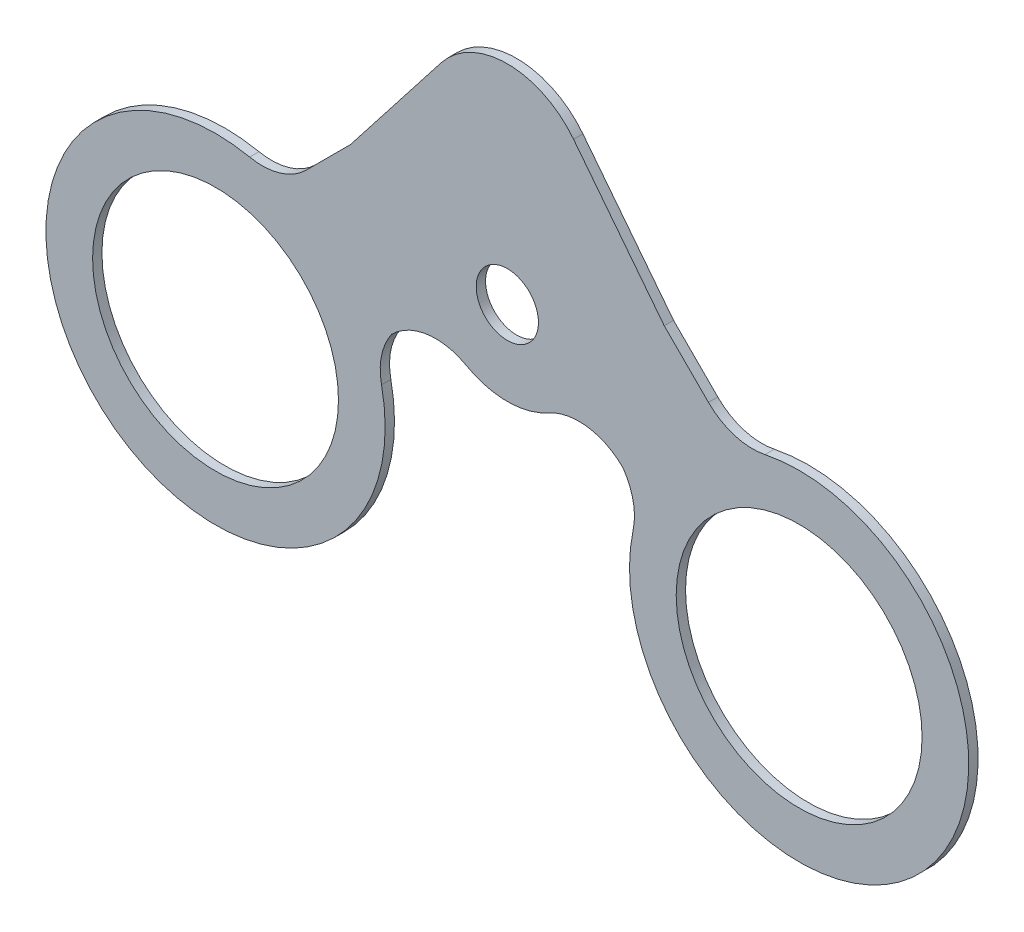
SolidWorks part; units mm, degrees
ref_plane "Спереди" through (0, 0, 0) normal (0, 0, 1) x (1, 0, 0)
ref_plane "Сверху" through (0, 0, 0) normal (0, 1, 0) x (1, 0, 0)
ref_plane "Справа" through (0, 0, 0) normal (1, 0, 0) x (0, 0, -1)
sketch "Эскиз1" plane through (0, 0, 0) normal (0, 0, 1) x (1, 0, 0)
  line L0 (-93.75, 0) -> (93.75, 0) construction
  line L1 (-93.75, 0) -> (0, 53.75) construction
  line L2 (0, 53.75) -> (93.75, 0) construction
  line L3 (93.75, 0) -> (93.75, -40) construction
  line L4 (0, 53.75) -> (53.75, -40) construction
  line L5 (93.75, -40) -> (53.75, -40) construction
  line L26 (0, 53.75) -> (-93.75, 53.75) construction
  line L27 (-93.75, 0) -> (0, 93.75) construction
  line L28 (0, 93.75) -> (93.75, 0) construction
  line L29 (-73.0386, 50.4112) -> (-50.4112, 73.0386)
  line L30 (-23.5342, 40.516) -> (-43.3388, 20.7114)
  line L31 (-61.7249, 61.7249) -> (-32.0251, 32.0251) construction
  line L32 (43.3388, 20.7114) -> (23.5342, 40.516)
  line L33 (73.0386, 50.4112) -> (50.4112, 73.0386)
  line L36 (-50.4112, 73.0386) -> (-21.2856, 110.3609)
  line L37 (50.4112, 73.0386) -> (21.2856, 110.3609)
  circle A0 centre (0, 53.75) radius 8.075 construction
  circle A3 centre (-93.75, 0) radius 39.5
  circle A4 centre (93.75, 0) radius 39.5
  arc A5 (-73.0386, 50.4112) -> (-43.3388, 20.7114) centre (-93.75, 0) ccw
  arc A6 (43.3388, 20.7114) -> (73.0386, 50.4112) centre (93.75, 0) ccw
  circle A8 centre (0, 53.75) radius 10
  circle A9 centre (0, 93.75) radius 20 construction
  circle A11 centre (0, 53.75) radius 20 construction
  circle A12 centre (-93.75, 0) radius 49.06 construction
  circle A13 centre (0, 93.75) radius 49.06 construction
  circle A17 centre (93.75, 0) radius 49.06 construction
  circle A18 centre (0, 93.75) radius 54.5 construction
  arc A20 (21.2856, 110.3609) -> (-21.2856, 110.3609) centre (0, 93.75) ccw
  circle A21 centre (0, 93.75) radius 27 construction
  circle A22 centre (-93.75, 0) radius 54.5 construction
  arc A23 (-23.5342, 40.516) -> (23.5342, 40.516) centre (0, 53.75) ccw
  circle A24 centre (93.75, 0) radius 54.5 construction
  point P2 (0, 0)
  point P28 (-46.875, 46.875)
  point P34 (0, 0)
  dimension "D6" = 16.15
  dimension "D4" = 79
  dimension "D8" = 20
  dimension "D9" = 40
  dimension "D11" = 98.12
  dimension "D1" = 187.5
  dimension "D2" = 53.75
  dimension "D3" = 40
  dimension "D10" = 29.827
  dimension "D13" = 32
  dimension "D12" = 7
  dimension "D5" = 15
  dimension "D7" = 15
  dimension "D14" = 7
extrude "Бобышка-Вытянуть1" add sketch "Эскиз1" along normal blind 3
fillet "Скругление1" radius 20 2 edges at (23.5342, 40.516, 1.5) (-23.5342, 40.516, 1.5)
fillet "Скругление2" radius 20 4 edges at (73.0386, 50.4112, 1.5) (-73.0386, 50.4112, 1.5) (43.3388, 20.7114, 1.5) (-43.3388, 20.7114, 1.5)
equation "\"R\"= 75мм'Радиус колеса"
equation "\"X\"= 2.5 * \"R\"'Расстояние между осями колёс"
equation "\"dX\"= \"X\" - 2 * \"R\"'Расстояние между поверхностями колёс"
equation "\"__3dp_diam\"= 0.15мм'Допуск диаметров для 3Д печати"
equation "\"__3dp_line\"= 0.05мм'Допуск линейных размеров для 3Д печати"
equation "\"D1@Эскиз1\"=\"X\""
equation "\"Y\"= \"X\" / 2 - \"h\"'Расстояние между плоскостью осей и осью балансира (через линейное отклонение)"
equation "\"h\"= 40'Максимально допустимое отклонение балансира от нормали"
equation "\"D2@Эскиз1\"=\"Y\""
equation "\"D3@Эскиз1\"=\"h\""
equation "\"D6@Эскиз1\"=\"__3dp_diam\" + 16мм"
